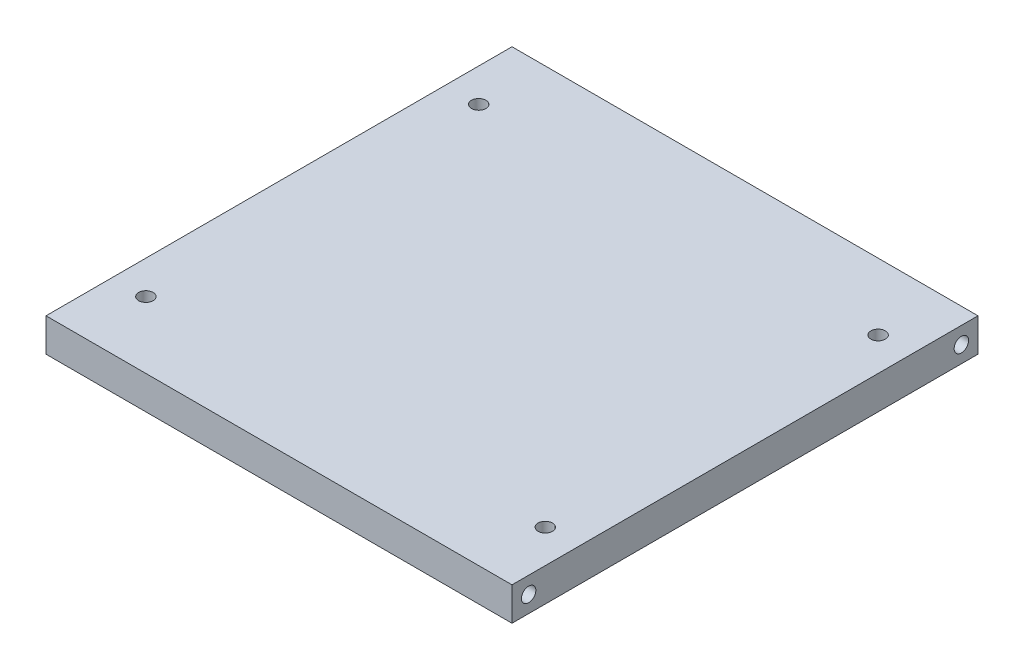
SolidWorks part; units mm, degrees
material "AISI 1020"
ref_plane "Front Plane" through (0, 0, 0) normal (0, 0, 1) x (1, 0, 0)
ref_plane "Top Plane" through (0, 0, 0) normal (0, 1, 0) x (1, 0, 0)
ref_plane "Right Plane" through (0, 0, 0) normal (1, 0, 0) x (0, 0, -1)
sketch "Sketch1" plane through (0, 0, 0) normal (0, 1, 0) x (1, 0, 0)
  line L1 (0, 0) -> (84, 0)
  line L2 (0, 0) -> (0, 84)
  line L3 (0, 84) -> (84, 84)
  line L4 (84, 0) -> (84, 84)
  dimension "D1" = 84
  dimension "D2" = 84
extrude "Boss-Extrude1" add sketch "Sketch1" along normal blind 6
sketch "Sketch2" plane through (0, 6, 0) normal (0, 1, 0) x (1, 0, 0)
  line L0 (84, 84) -> (0, 84) construction
  line L1 (0, 84) -> (0, 0) construction
  circle A0 centre (6, 72) radius 1.3
  dimension "D1" = 2.6
  dimension "D3" = 6
  dimension "D2" = 12
extrude "Cut-Extrude1" cut sketch "Sketch2" against normal blind 6
pattern_linear "LPattern1" count 2 spacing 72 along (1, 0, 0) count 2 spacing 60 along (0, 0, 1) of "Cut-Extrude1"
sketch "Sketch3" plane through (0, 0, 0) normal (-1, 0, 0) x (0, 0, 1)
  line L0 (-84, 3) -> (-3, 3) construction
  line L1 (-84, 6) -> (-84, 0) construction
  line L2 (0, 6) -> (0, 0) construction
  circle A0 centre (-81, 3) radius 1.3
  circle A1 centre (-3, 3) radius 1.3
  dimension "D1" = 3
  dimension "D3" = 2.6
  dimension "D4" = 2.6
  dimension "D2" = 3
extrude "Cut-Extrude2" cut sketch "Sketch3" against normal blind 10
ref_plane "Plane1" through (42, 0, 0) normal (-1, 0, 0) x (0, 0, 1)
mirror "Mirror1" about plane through (42, 0, 0) normal (-1, 0, 0) of "Cut-Extrude2"
